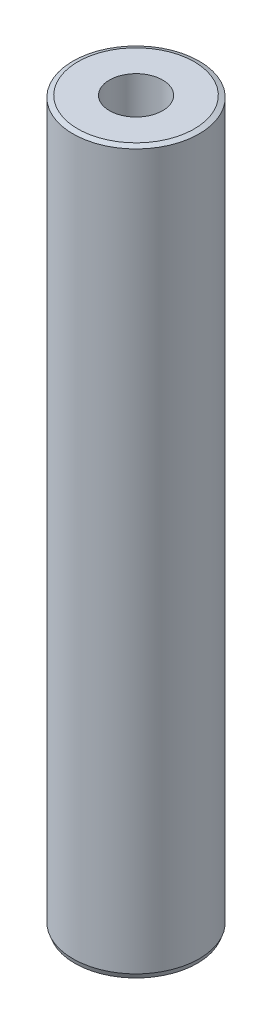
SolidWorks part; units mm, degrees
ref_plane "Front Plane" through (0, 0, 0) normal (0, 0, 1) x (1, 0, 0)
ref_plane "Top Plane" through (0, 0, 0) normal (0, 1, 0) x (1, 0, 0)
ref_plane "Right Plane" through (0, 0, 0) normal (1, 0, 0) x (0, 0, -1)
sketch "Sketch1" plane through (0, 0, 0) normal (0, 1, 0) x (1, 0, 0)
  circle A0 centre (0, 0) radius 52.5
  dimension "SHAFT_OD" = 105
extrude "Boss-Extrude1" add sketch "Sketch1" along normal blind 600
sketch "Sketch2" plane through (0, 0, 0) normal (0, 1, 0) x (1, 0, 0)
  circle A0 centre (0, 0) radius 22.1296
  dimension "BORE_D" = 44.2592
extrude "Cut-Extrude1" cut sketch "Sketch2" along normal through all
chamfer "Chamfer1" distance 1.5326 angle 69.337 2 edges at (0, 600, 52.5) (0, 0, 52.5) first distance on face at (0, 600, 52.5) first distance on face at (0, 0, 22.1296)
